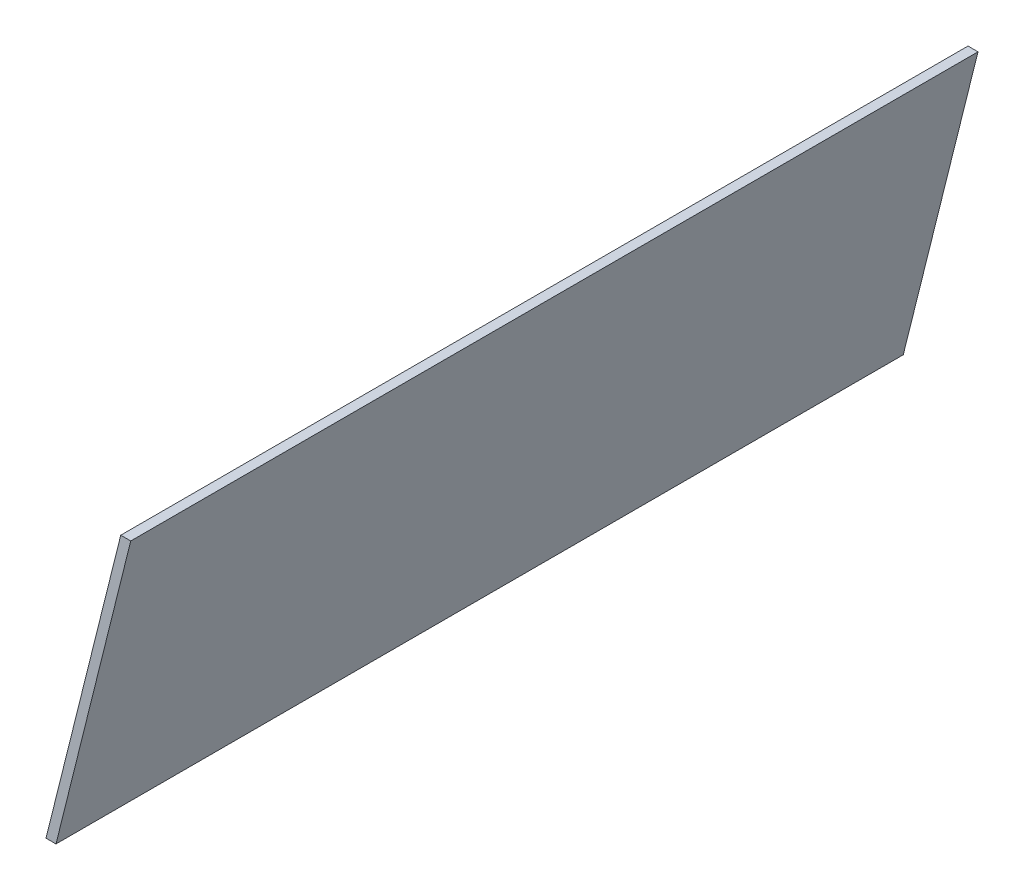
SolidWorks part; units mm, degrees
material "5052-H34"
ref_plane "Front Plane" through (0, 0, 0) normal (0, 0, 1) x (1, 0, 0)
ref_plane "Top Plane" through (0, 0, 0) normal (0, 1, 0) x (1, 0, 0)
ref_plane "Right Plane" through (0, 0, 0) normal (1, 0, 0) x (0, 0, -1)
sketch "Sketch1" plane through (0, 0, 0) normal (0, 0, 1) x (1, 0, 0)
  line L0 (-40.9017, -38.8249) -> (-37.6295, -38.8249)
  line L1 (-37.6295, -38.8249) -> (-13.1517, 59.3501)
  line L2 (-40.9017, -38.8249) -> (-16.4239, 59.3501)
  line L3 (-13.1517, 59.3501) -> (-16.4239, 59.3501)
  dimension "D1" = 104
  dimension "D2" = 98.175
  dimension "D3" = 3.175
extrude "Boss-Extrude1" add sketch "Sketch1" along normal blind 277.475 contours L1 L3 L2 L0
